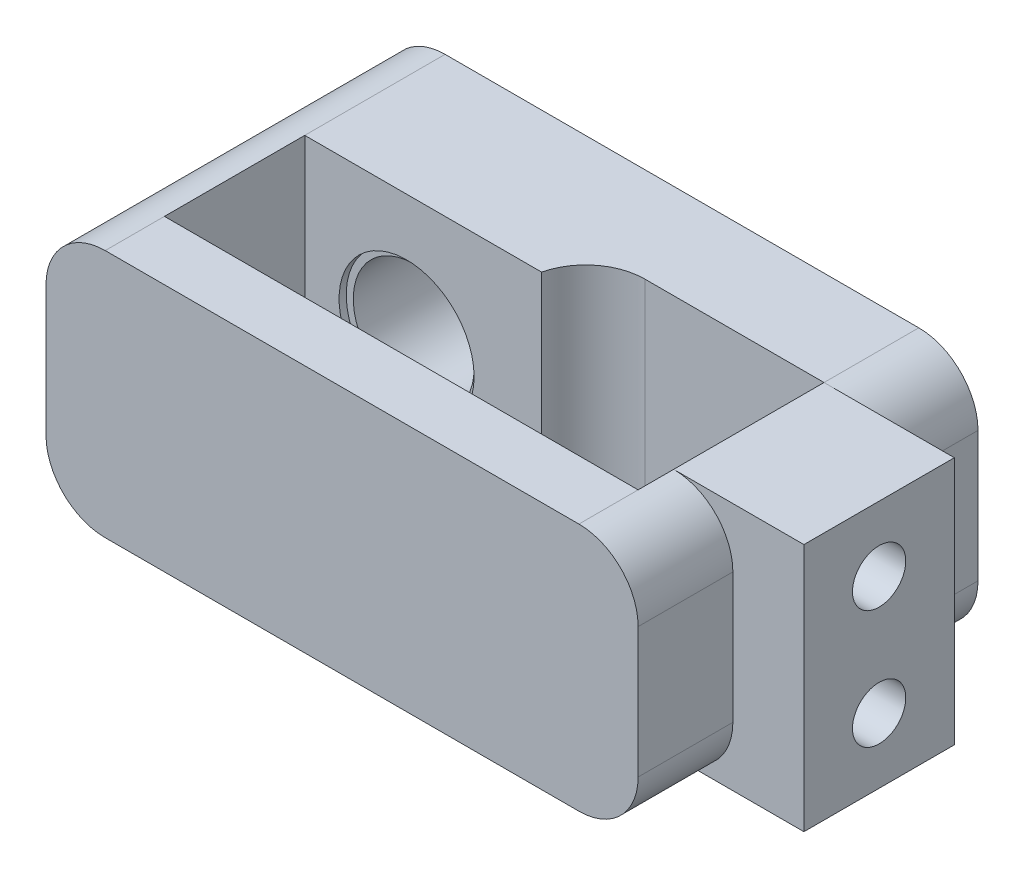
SolidWorks part; units mm, degrees
ref_plane "Front Plane" through (0, 0, 0) normal (0, 0, 1) x (1, 0, 0)
ref_plane "Top Plane" through (0, 0, 0) normal (0, 1, 0) x (1, 0, 0)
ref_plane "Right Plane" through (0, 0, 0) normal (1, 0, 0) x (0, 0, -1)
sketch "Sketch1" plane through (0, 0, 0) normal (0, 1, 0) x (1, 0, 0)
  line L1 (-20, 2.5) -> (20, 2.5)
  line L2 (-20, 2.5) -> (-20, -9.35)
  line L3 (-20, -9.35) -> (20, -9.35)
  line L4 (20, 2.5) -> (20, -9.35)
  line L7 (-25, 14.35) -> (25, 14.35)
  line L8 (-25, 14.35) -> (-25, -14.35)
  line L9 (-25, -14.35) -> (25, -14.35)
  line L10 (25, 14.35) -> (25, -14.35)
  point P0 (0, 0)
  point P6 (0, -9.35)
  point P7 (0, 0)
  point P12 (0, -14.35)
  point P13 (25, 0)
  dimension "D1" = 5
  dimension "D2" = 11.85
  dimension "D3" = 50
  dimension "D4" = 28.7
  dimension "D5" = 5
extrude "Boss-Extrude1" add sketch "Sketch1" along normal blind 21
sketch "Sketch4" plane through (0, 0, -2.5) normal (0, 0, 1) x (1, 0, 0)
  line L0 (-25, 21) -> (-25, 0) construction
  point P0 (-11.4, 10.5)
  point P7 (-25, 10.5)
  dimension "D1" = 13.6
sketch "Sketch9" plane through (20, 0, 0) normal (-1, 0, 0) x (0, 0, 1)
  line L0 (0, 15.5) -> (0, 5.5) construction
  line L2 (14.35, 21) -> (14.35, 0) construction
  point P0 (0, 15.5)
  point P2 (0, 5.5)
  point P11 (14.35, 10.5)
  point P12 (0, 10.5)
  dimension "D1" = 10
hole_wizard "Hole1" positions "Sketch4" profile "Sketch3" legacy end condition up to next
sketch "Sketch3" plane through (-11.4, 10.5, -2.5) normal (1, 0, 0) x (0, -1, 0)
  line L0 (0, 0) -> (0, 11.85)
  line L1 (0, 11.85) -> (5.1, 11.85)
  line L2 (5.1, 11.85) -> (5.1, 0.6)
  line L3 (5.1, 0.6) -> (5.7, 0.6)
  line L4 (5.7, 0.6) -> (5.7, 0)
  line L5 (5.7, 0) -> (0, 0)
  line L6 (0, 110) -> (0, -10) construction
  dimension "Diameter" = 10.2
  dimension "Depth" = 11.85
  dimension "C-Bore Diameter" = 11.4
  dimension "C-Bore Depth" = 0.6
sketch "Sketch10" plane through (25, 0, 0) normal (1, 0, 0) x (0, 0, -1)
  line L0 (-14.35, 21) -> (14.35, 21) construction
  line L1 (-6.35, 21) -> (6.35, 21)
  line L2 (-6.35, 21) -> (-6.35, 0)
  line L3 (-6.35, 0) -> (6.35, 0)
  line L4 (6.35, 21) -> (6.35, 0)
  line L5 (-14.35, 0) -> (14.35, 0) construction
  point P8 (0, 0)
  dimension "D1" = 12.7
extrude "Boss-Extrude2" add sketch "Sketch10" along normal blind 6
hole_wizard "M4 Clearance Hole1" positions "Sketch9" profile "Sketch8" hole size "M4" standard "ANSI Metric" end condition through all
sketch "Sketch8" plane through (20, 15.5, 0) normal (0, 1, 0) x (0, 0, 1)
  line L0 (0, 0) -> (0, 11)
  line L1 (0, 11) -> (2.25, 11)
  line L2 (2.25, 11) -> (2.25, 0.025)
  line L3 (2.25, 0.025) -> (2.275, 0)
  line L5 (2.275, 0) -> (0, 0)
  line L6 (-2.25, 0.025) -> (-2.275, 0) construction
  line L11 (0, -6.35) -> (0, 107.95) construction
  dimension "Thru Hole Dia." = 4.5
  dimension "Thru Hole Depth" = 11
  dimension "Near C'Sink Dia." = 4.55
  dimension "Near C'Sink Angle" = 90
sketch "Sketch11" plane through (0, 21, 0) normal (0, 1, 0) x (1, 0, 0)
  line L1 (20, 2.5) -> (0, 2.5)
  line L2 (20, 2.5) -> (20, 6.35)
  line L3 (20, 6.35) -> (0, 6.35)
  line L4 (0, 2.5) -> (0, 6.35)
extrude "Cut-Extrude1" cut sketch "Sketch11" against normal through all
fillet "Fillet1" radius 5 7 edges at (25, 0, -10.35) (25, 21, -10.35) (25, 0, 10.35) (25, 21, 10.35) (-25, 0, 0) (0, 10.5, -6.35) (-25, 21, 0)
